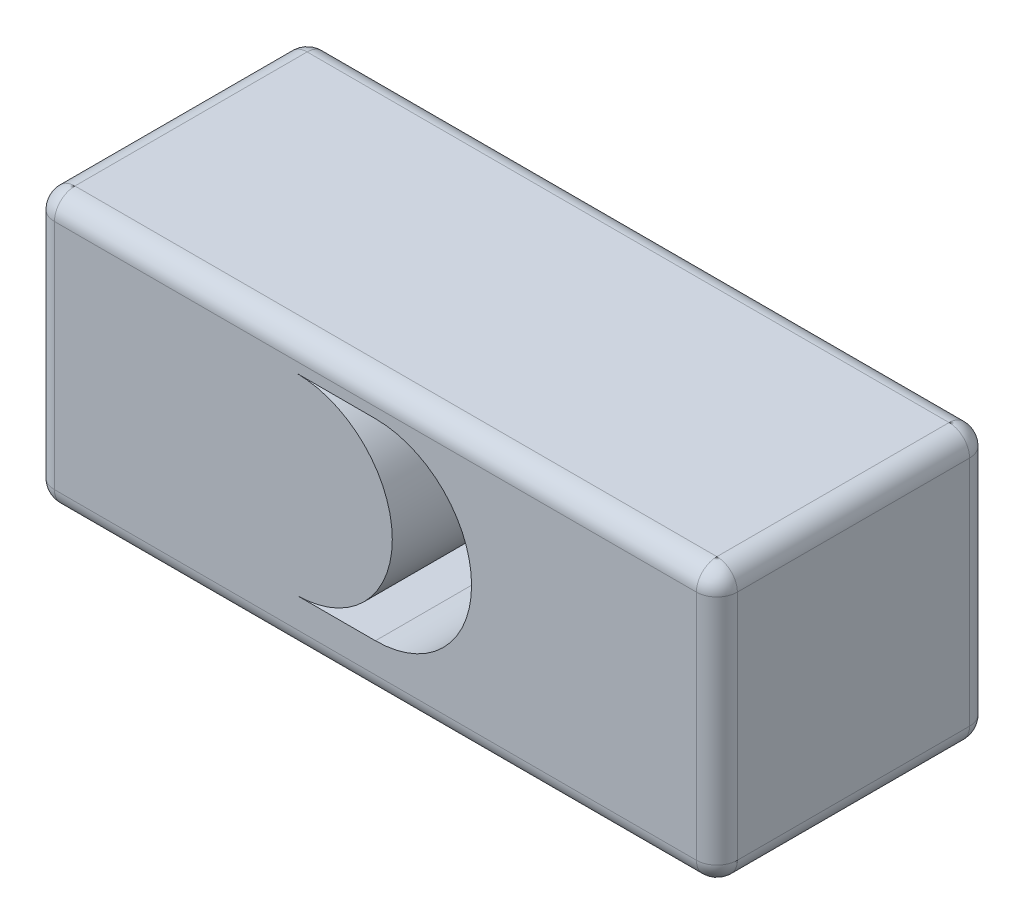
SolidWorks part; units mm, degrees
ref_plane "Plan de face" through (0, 0, 0) normal (0, 0, 1) x (1, 0, 0)
ref_plane "Plan de dessus" through (0, 0, 0) normal (0, 1, 0) x (1, 0, 0)
ref_plane "Plan de droite" through (0, 0, 0) normal (1, 0, 0) x (0, 0, -1)
sketch "Esquisse1" plane through (0, 0, 0) normal (0, 0, 1) x (1, 0, 0)
  line L1 (-0.22, 0) -> (0.28, 0)
  line L2 (-0.22, 0) -> (-0.22, -0.2)
  line L3 (-0.22, -0.2) -> (0.28, -0.2)
  line L4 (0.28, 0) -> (0.28, -0.2)
  dimension "D1" = 0.5
  dimension "D2" = 0.2
extrude "Boss.-Extru.1" add sketch "Esquisse1" along normal blind 0.2
sketch "Esquisse2" plane through (0, 0, 0.2) normal (0, 0, 1) x (1, 0, 0)
  line L0 (0.03, 0) -> (0.03, -0.2) construction
  line L1 (0.28, 0) -> (-0.22, 0) construction
  line L2 (-0.22, -0.2) -> (0.28, -0.2) construction
  line L3 (-0.028, -0.0225) -> (0.03, -0.0225)
  line L4 (-0.028, -0.1633) -> (0.03, -0.1633)
  arc A0 (0.03, -0.0225) -> (0.03, -0.1633) centre (0.03, -0.0929) cw
  arc A1 (-0.028, -0.0225) -> (-0.028, -0.1633) centre (-0.028, -0.0929) cw
extrude "Enlèv. mat.-Extru.3" cut sketch "Esquisse2" against normal through all
fillet "Congé1" radius 0.015 12 edges at (0.03, -0.2, 0.2) (0.03, -0.2, 0) (-0.22, -0.1, 0.2) (-0.22, -0.2, 0.1) (-0.22, -0.1, 0) (0.28, -0.2, 0.1) (0.28, -0.1, 0.2) (0.28, -0.1, 0) (0.28, 0, 0.1) (0.03, 0, 0.2) (-0.22, 0, 0.1) (0.03, 0, 0)
